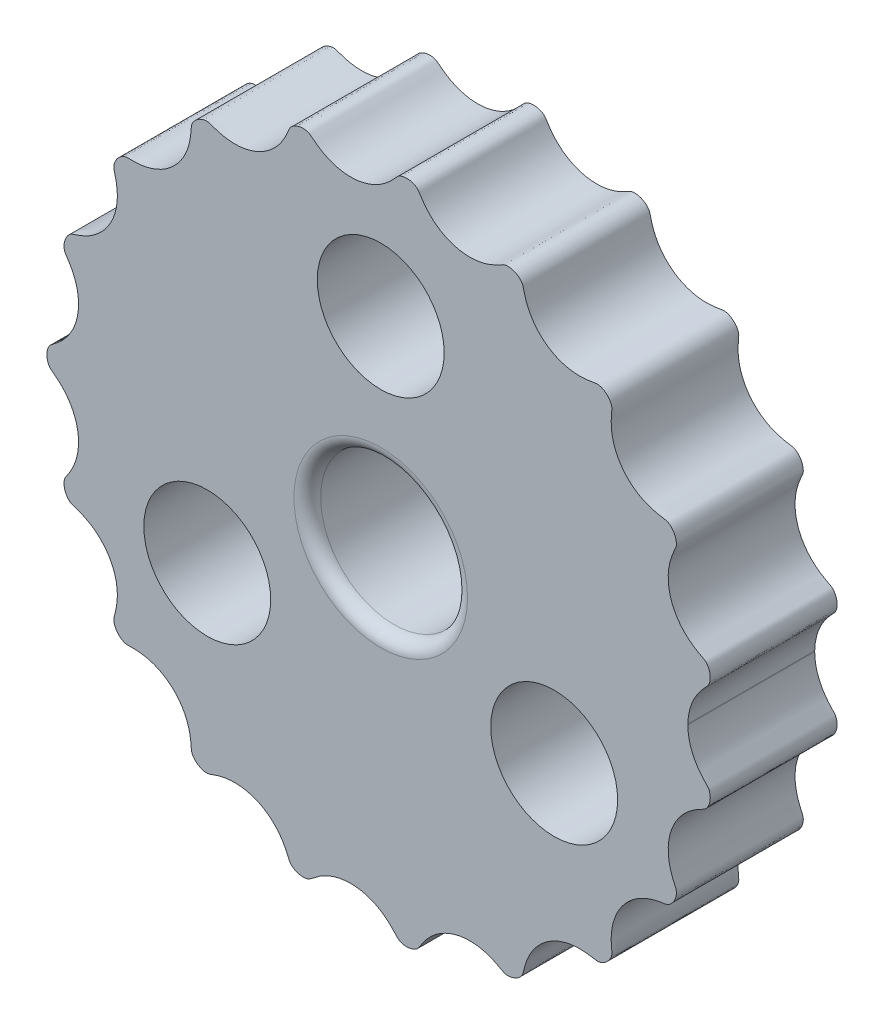
SolidWorks part; units mm, degrees
ref_plane "Ebene vorne" through (0, 0, 0) normal (0, 0, 1) x (1, 0, 0)
ref_plane "Ebene oben" through (0, 0, 0) normal (0, 1, 0) x (1, 0, 0)
ref_plane "Ebene rechts" through (0, 0, 0) normal (1, 0, 0) x (0, 0, -1)
sketch "Skizze1" plane through (0, 0, 0) normal (0, 0, 1) x (1, 0, 0)
  circle A0 centre (0, 0) radius 25
  dimension "D1" = 50
extrude "Aufsatz-Linear austragen1" add sketch "Skizze1" along normal blind 9.5 contours A0
sketch "Skizze3" plane through (0, 0, 9.5) normal (0, 0, 1) x (1, 0, 0)
  circle A0 centre (0, 25) radius 0.5
  circle A1 centre (0, 0) radius 25 construction
extrude "Schnitt-Linear austragen1" cut sketch "Skizze3" against normal up to next contours A0
pattern_circular "Kreismuster3" [suppressed] count 30 over 360 of bodies 102
sketch "Skizze9" plane through (0, 0, 9.5) normal (0, 0, 1) x (1, 0, 0)
  line L0 (23.0004, 0.0609) -> (23, 0)
  spline S0 degree 4 poles (21.8349, 10.4363) (21.7595, 10.2402) (21.6296, 9.8393) (21.51, 9.2154) (21.5169, 8.368) (21.6949, 7.529) (21.9996, 6.8362) (22.3616, 6.2918) (22.7278, 5.8789) (23.0126, 5.6175) (23.2743, 5.4145) (23.4929, 5.2661) (23.6607, 5.1622) (23.8217, 5.0701) (23.9556, 4.9977) (24.0711, 4.9376) (24.1728, 4.8842) (24.259, 4.8347) (24.3648, 4.7517) (24.4596, 4.6337) (24.5411, 4.4963) (24.6203, 4.3033) (24.6742, 4.0826) (24.6893, 3.8352) (24.654, 3.6047) (24.5939, 3.4337) (24.5231, 3.3149) (24.4482, 3.2274) (24.3391, 3.1139) (24.2149, 2.9815) (24.0838, 2.8346) (23.9185, 2.6346) (23.746, 2.4006) (23.5642, 2.1174) (23.3859, 1.7712) (23.2392, 1.419) (23.1381, 1.082) (23.0724, 0.8012) (23.0325, 0.5259) (23.0102, 0.3454) (22.9992, 0.0775) (22.999, -0.0665) (23.009, -0.3222) (23.0286, -0.4951) (23.0652, -0.7605) (23.1283, -1.0483) (23.2566, -1.484) (23.4559, -1.9318) (23.6809, -2.3132) (23.9099, -2.6224) (24.0743, -2.8241) (24.2067, -2.9723) (24.3336, -3.1084) (24.4467, -3.2256) (24.524, -3.3159) (24.583, -3.4156) (24.6246, -3.5208) (24.6638, -3.6686) (24.6852, -3.8609) (24.6735, -4.0869) (24.6205, -4.3068) (24.5464, -4.4848) (24.4695, -4.6144) (24.4037, -4.7024) (24.3311, -4.7784) (24.2516, -4.8395) (24.1377, -4.9039) (24.0001, -4.974) (23.846, -5.0565) (23.6352, -5.1762) (23.3933, -5.3292) (23.1212, -5.5276) (22.8316, -5.7799) (22.5655, -6.0569) (22.2617, -6.4361) (21.9548, -6.9332) (21.7249, -7.4811) (21.5829, -8.0653) (21.5273, -8.5636) (21.5216, -8.9708) (21.5541, -9.3694) (21.6218, -9.7561) (21.7087, -10.0818) (21.7995, -10.3483) (21.8842, -10.5632) (21.9558, -10.729) (22.0248, -10.8829) (22.0924, -11.0248) (22.1404, -11.1746) (22.1504, -11.3468) (22.1274, -11.5442) (22.061, -11.7619) (21.9505, -11.9788) (21.8083, -12.1674) (21.6614, -12.3022) (21.5247, -12.3914) (21.414, -12.4372) (21.3301, -12.4586) (21.2321, -12.4761) (21.1212, -12.4922) (20.9921, -12.5121) (20.8374, -12.539) (20.6763, -12.5709) (20.4655, -12.6198) (20.1205, -12.7175) (19.6539, -12.8972) (19.0899, -13.2109) (18.4957, -13.6939) (17.9798, -14.3033) (17.5818, -15.0184) (17.3599, -15.7125) (17.2758, -16.2728) (17.2579, -16.6757) (17.2603, -16.9123) (17.2683, -17.0871) (17.2802, -17.2498) (17.2921, -17.3816) (17.3037, -17.4944) (17.3123, -17.5952) (17.3148, -17.684) (17.3037, -17.7848) (17.2728, -17.8946) (17.2143, -18.0352) (17.1157, -18.1992) (16.9706, -18.3697) (16.7741, -18.5306) (16.5633, -18.6445) (16.3771, -18.7041) (16.228, -18.7183) (16.1024, -18.7064) (15.9827, -18.6847) (15.837, -18.6581) (15.664, -18.6292) (15.4825, -18.6042) (15.2505, -18.5802) (14.9676, -18.5655) (14.5429, -18.5729) (14.0693, -18.6361) (13.6043, -18.7559) (13.0666, -18.9667) (12.6278, -19.2052) (12.2149, -19.5036) (11.8389, -19.8586) (11.5583, -20.1838) (11.3157, -20.5303) (11.1115, -20.893) (10.9662, -21.2192) (10.865, -21.4994) (10.7941, -21.7329) (10.7511, -21.8937) (10.717, -22.0322) (10.6867, -22.159) (10.6596, -22.2741) (10.6135, -22.4098) (10.5273, -22.5357) (10.4274, -22.6442) (10.2911, -22.7583) (10.1265, -22.8625) (9.947, -22.94) (9.7581, -22.9885) (9.581, -23.009) (9.446, -23.0074) (9.3222, -22.9883) (9.215, -22.9494) (9.1367, -22.9105) (9.0374, -22.8556) (8.9163, -22.7867) (8.7704, -22.7082) (8.5994, -22.6214) (8.2969, -22.4821) (7.9364, -22.3488) (7.5146, -22.2402) (7.0313, -22.1759) (6.6328, -22.1607) (6.2298, -22.1836) (5.826, -22.2463) (5.4253, -22.3496) (5.032, -22.4941) (4.6565, -22.6767) (4.3023, -22.8948) (3.9755, -23.1429) (3.6777, -23.4168) (3.4441, -23.6748) (3.264, -23.904) (3.127, -24.0974) (3.026, -24.2496) (2.9434, -24.3794) (2.8771, -24.486) (2.8107, -24.5788) (2.7442, -24.6523) (2.6543, -24.7214) (2.5172, -24.8007) (2.3431, -24.8698) (2.129, -24.9172) (1.9104, -24.9257) (1.7254, -24.9049) (1.5597, -24.8634) (1.4272, -24.8123) (1.3018, -24.7374) (1.1919, -24.6254) (1.0929, -24.5126) (0.9862, -24.3949) (0.8714, -24.2728) (0.7167, -24.1173) (0.5166, -23.934) (0.1944, -23.6752) (-0.2816, -23.3734) (-0.8873, -23.1037) (-1.633, -22.9219) (-2.4119, -22.88) (-3.1838, -22.9833) (-3.829, -23.1953) (-4.2989, -23.431) (-4.6166, -23.6302) (-4.8236, -23.7746) (-4.9777, -23.8915) (-5.1193, -24.0037) (-5.2422, -24.1039) (-5.3368, -24.1704) (-5.4383, -24.2183) (-5.5428, -24.2496) (-5.6869, -24.2756) (-5.8715, -24.2822) (-6.0864, -24.2562) (-6.2931, -24.1927) (-6.4597, -24.1129) (-6.6006, -24.0204) (-6.7112, -23.9272) (-6.7966, -23.8241) (-6.8508, -23.7158) (-6.8984, -23.6058) (-6.9474, -23.4882) (-7.0086, -23.3469) (-7.0843, -23.183) (-7.1853, -22.982) (-7.3178, -22.7471) (-7.4915, -22.481) (-7.7159, -22.1922) (-7.9683, -21.919) (-8.2484, -21.6651) (-8.561, -21.4293) (-9, -21.1594) (-9.4852, -20.944) (-10.0058, -20.7949) (-10.5401, -20.7187) (-10.9664, -20.7017) (-11.386, -20.7263) (-11.7441, -20.7819) (-12.0407, -20.8508) (-12.2801, -20.9199) (-12.4645, -20.9804) (-12.619, -21.0347) (-12.7443, -21.0813) (-12.8432, -21.1127) (-12.9148, -21.1293) (-13.0155, -21.1409) (-13.1607, -21.1341) (-13.3458, -21.0947) (-13.5626, -21.0052) (-13.7727, -20.87) (-13.9463, -20.7079) (-14.067, -20.5439) (-14.1433, -20.3907) (-14.1772, -20.2506) (-14.1869, -20.1194) (-14.1984, -19.9464) (-14.2135, -19.7574) (-14.2357, -19.56) (-14.2744, -19.3096) (-14.3484, -18.9507) (-14.4988, -18.4602) (-14.7821, -17.8614) (-15.2347, -17.2299) (-15.8123, -16.6797) (-16.4915, -16.2457) (-17.1512, -15.9856) (-17.6884, -15.8653) (-18.0779, -15.8187) (-18.3444, -15.8008) (-18.5515, -15.7964) (-18.7472, -15.7971) (-18.9192, -15.8013) (-19.043, -15.798) (-19.1585, -15.7742) (-19.2639, -15.7342) (-19.3981, -15.6643) (-19.5524, -15.5524) (-19.7098, -15.3942) (-19.8355, -15.2104) (-19.9175, -15.0392) (-19.9694, -14.8748) (-19.9942, -14.7409) (-19.9941, -14.6091) (-19.9622, -14.4594) (-19.9209, -14.3132) (-19.8775, -14.147) (-19.8227, -13.9154) (-19.7703, -13.6388) (-19.7298, -13.3095) (-19.7155, -12.9316) (-19.7343, -12.5536) (-19.7865, -12.1771) (-19.8725, -11.8051) (-20.0235, -11.3478) (-20.2355, -10.9007) (-20.5061, -10.4779) (-20.8313, -10.0898) (-21.1296, -9.7984) (-21.4493, -9.5419) (-21.7859, -9.3207) (-22.0908, -9.1576) (-22.3541, -9.0395) (-22.5745, -8.9534) (-22.7489, -8.8919) (-22.9125, -8.8369) (-23.0664, -8.7897) (-23.2127, -8.7239) (-23.3488, -8.6133) (-23.48, -8.461) (-23.5959, -8.2631) (-23.6806, -8.0335) (-23.7223, -7.802) (-23.7216, -7.6015) (-23.6936, -7.4372) (-23.6459, -7.3113) (-23.587, -7.2131) (-23.5046, -7.0919) (-23.4135, -6.9559) (-23.317, -6.8055) (-23.1954, -6.601) (-23.0687, -6.3633) (-22.9383, -6.0757) (-22.7839, -5.6451) (-22.656, -5.1008) (-22.5992, -4.4221) (-22.6826, -3.6209) (-22.9272, -2.8308) (-23.2818, -2.1836) (-23.6363, -1.7308) (-23.9221, -1.4366) (-24.1011, -1.2722) (-24.239, -1.1546) (-24.372, -1.0482) (-24.4823, -0.963) (-24.578, -0.8915) (-24.662, -0.827) (-24.7323, -0.7672) (-24.8009, -0.6902) (-24.8613, -0.5932) (-24.925, -0.4573) (-24.9789, -0.2784) (-25.008, -0.0615) (-24.998, 0.1569) (-24.9616, 0.3399) (-24.9066, 0.5001) (-24.8504, 0.6156) (-24.7832, 0.7138) (-24.7061, 0.7903) (-24.6412, 0.8433) (-24.5549, 0.909) (-24.4487, 0.9887) (-24.3242, 1.0855) (-24.1833, 1.2011) (-24.0105, 1.3531) (-23.8111, 1.5469) (-23.5946, 1.788) (-23.3715, 2.0829) (-23.1734, 2.3976) (-23.0026, 2.7303) (-22.8251, 3.1685) (-22.6969, 3.6432) (-22.6277, 4.1442) (-22.6242, 4.6617) (-22.6664, 5.0951) (-22.7519, 5.5174) (-22.8777, 5.9244) (-23.0193, 6.2625) (-23.1587, 6.5356) (-23.2844, 6.7524) (-23.3883, 6.9169) (-23.4888, 7.0702) (-23.5875, 7.2108) (-23.6712, 7.3568) (-23.7142, 7.5309) (-23.7261, 7.7309) (-23.6995, 7.9535) (-23.6303, 8.1831) (-23.5263, 8.3908) (-23.4082, 8.549) (-23.2912, 8.6625) (-23.187, 8.7339) (-23.0968, 8.7758) (-22.9816, 8.8159) (-22.8484, 8.8583) (-22.6971, 8.9097) (-22.4871, 8.9859) (-22.2435, 9.0865) (-21.9662, 9.221) (-21.6596, 9.4005) (-21.366, 9.6063) (-21.0151, 9.8992) (-20.6164, 10.3191) (-20.2771, 10.8105) (-20.0144, 11.3636) (-19.8542, 11.8663) (-19.7673, 12.2789) (-19.7222, 12.6923) (-19.7169, 13.1024) (-19.7451, 13.4552) (-19.7902, 13.7494) (-19.8394, 13.9878) (-19.8839, 14.1718) (-19.9244, 14.3263) (-19.9596, 14.452) (-19.9815, 14.5509) (-19.9911, 14.6219) (-19.9935, 14.7217) (-19.9742, 14.8643) (-19.9195, 15.0445) (-19.8125, 15.2522) (-19.6794, 15.4254) (-19.5437, 15.5557) (-19.4017, 15.6607) (-19.2787, 15.7293) (-19.1504, 15.7794) (-19.0246, 15.7985) (-18.927, 15.8005) (-18.8133, 15.7991) (-18.6836, 15.7969) (-18.532, 15.7969) (-18.3106, 15.8023) (-18.0413, 15.8209) (-17.7248, 15.8628) (-17.3647, 15.941) (-16.9178, 16.0786) (-16.3974, 16.3085) (-15.8239, 16.6734) (-15.2485, 17.213) (-14.783, 17.8542) (-14.4878, 18.4827) (-14.3351, 18.9986) (-14.2627, 19.3751) (-14.2269, 19.6306) (-14.2075, 19.8274) (-14.1936, 20.0116) (-14.184, 20.1733) (-14.1697, 20.2905) (-14.1362, 20.4005) (-14.0873, 20.5015) (-14.0059, 20.6294) (-13.8804, 20.7742) (-13.7077, 20.9182) (-13.5127, 21.0276) (-13.335, 21.0939) (-13.1647, 21.1311) (-13.0232, 21.1444) (-12.8817, 21.1276) (-12.7469, 21.0817) (-12.6315, 21.0398) (-12.5001, 20.993) (-12.3519, 20.9431) (-12.1413, 20.8781) (-11.8655, 20.8075) (-11.5389, 20.7468) (-11.1616, 20.7097) (-10.7833, 20.7056) (-10.3038, 20.7432) (-9.7354, 20.8584) (-9.1818, 21.0633) (-8.6608, 21.3563) (-8.2599, 21.6542) (-7.9581, 21.9276) (-7.6875, 22.2243) (-7.4782, 22.5013) (-7.318, 22.7492) (-7.2006, 22.9556) (-7.1162, 23.1178) (-7.0401, 23.2775) (-6.9792, 23.4143) (-6.929, 23.5322) (-6.8829, 23.6417) (-6.8396, 23.7425) (-6.7732, 23.8583) (-6.6528, 23.9827) (-6.4911, 24.0996) (-6.2848, 24.1982) (-6.0489, 24.2635) (-5.8125, 24.2858) (-5.6133, 24.2679) (-5.4554, 24.2266) (-5.3475, 24.1752) (-5.2756, 24.1275) (-5.1963, 24.0667) (-5.1084, 23.9955) (-5.0052, 23.9133) (-4.8796, 23.817) (-4.7458, 23.7196) (-4.5657, 23.5973) (-4.2579, 23.4095) (-3.8065, 23.1883) (-3.1897, 22.9875) (-2.4297, 22.8812) (-1.6328, 22.9188) (-0.8411, 23.1135) (-0.1854, 23.421) (0.2799, 23.7378) (0.5861, 23.9964) (0.7572, 24.1576) (0.8795, 24.2813) (0.9904, 24.3996) (1.0788, 24.4971) (1.1534, 24.5815) (1.2215, 24.6556) (1.2849, 24.7171) (1.366, 24.7765) (1.4665, 24.8274) (1.6073, 24.879) (1.7912, 24.9173) (2.0109, 24.9275) (2.2284, 24.8982) (2.4076, 24.8457) (2.5635, 24.7759) (2.6787, 24.7064) (2.7776, 24.6216) (2.853, 24.522) (2.9089, 24.4353) (2.9741, 24.3312) (3.0513, 24.2111) (3.1673, 24.0378) (3.3314, 23.8136) (3.5412, 23.5623) (3.803, 23.2967) (4.0867, 23.0548) (4.3911, 22.8375) (4.7145, 22.6472) (5.1434, 22.4443) (5.6099, 22.2897) (6.1032, 22.1928) (6.6136, 22.1597) (7.04, 22.1755) (7.456, 22.233) (7.8578, 22.329) (8.1935, 22.443) (8.4659, 22.558) (8.6842, 22.6634) (8.8514, 22.7516) (9.0063, 22.8365) (9.1484, 22.9196) (9.3008, 22.9869) (9.4518, 23.0083) (9.5997, 23.0081) (9.7768, 22.9846) (9.9657, 22.9334) (10.1449, 22.8528) (10.3091, 22.7455) (10.4441, 22.6278) (10.5341, 22.5264) (10.6032, 22.4212) (10.6459, 22.3149) (10.6698, 22.2304) (10.6965, 22.1196) (10.7284, 21.9833) (10.7696, 21.8219) (10.8224, 21.6365) (10.926, 21.3181) (11.074, 20.9612) (11.2824, 20.576) (11.5658, 20.1761) (11.8273, 19.8724) (12.1194, 19.5924) (12.4404, 19.3397) (12.8767, 19.0608) (13.3474, 18.8414) (13.8414, 18.6865) (14.3466, 18.5977) (14.6978, 18.5693) (14.9983, 18.5678) (15.2424, 18.5806) (15.4319, 18.5983) (15.6163, 18.622) (15.7956, 18.651) (15.9629, 18.6804) (16.1188, 18.7114) (16.2634, 18.7186) (16.3919, 18.6957) (16.5434, 18.6484) (16.7128, 18.5663) (16.8932, 18.44) (17.0477, 18.2836) (17.1576, 18.1324) (17.2387, 17.9815) (17.2904, 17.8485) (17.3189, 17.7045) (17.3093, 17.5471) (17.2934, 17.3968) (17.2791, 17.2377) (17.2672, 17.07) (17.2581, 16.8499) (17.2594, 16.5774) (17.2886, 16.1632) (17.3914, 15.6061) (17.6071, 14.9758) (17.9828, 14.3047) (18.4824, 13.7066) (19.0811, 13.2137) (19.6713, 12.887) (20.16, 12.7034) (20.5195, 12.6059) (20.7644, 12.5521) (20.9536, 12.5182) (21.1309, 12.4903) (21.2868, 12.4679) (21.399, 12.4432) (21.5025, 12.4008) (21.5963, 12.345) (21.7134, 12.2561) (21.8437, 12.1238) (21.9702, 11.9469) (22.0634, 11.7504) (22.117, 11.5726) (22.1436, 11.4054) (22.149, 11.2598) (22.129, 11.1267) (22.0845, 11.0132) (22.035, 10.903) (21.9816, 10.7867) (21.919, 10.6454) (21.8499, 10.4782) (21.7706, 10.2666) (21.6878, 10.0086) (21.6103, 9.6986) (21.5509, 9.3355) (21.5224, 8.9626) (21.5272, 8.5827) (21.5787, 8.0866) (21.6972, 7.5846) (21.8865, 7.0905) (22.1457, 6.6199) (22.3909, 6.2662) (22.6666, 5.9438) (22.9679, 5.6541) (23.2503, 5.43) (23.5008, 5.2597) (23.7129, 5.1314) (23.8814, 5.0373) (24.0251, 4.9609) (24.1437, 4.9005) (24.2332, 4.8492) (24.2935, 4.8079) (24.37, 4.7415) (24.4633, 4.6297) (24.5599, 4.466) (24.6407, 4.2447) (24.683, 3.9972) (24.6804, 3.7586) (24.6403, 3.558) (24.5776, 3.3979) (24.4956, 3.2786) (24.4048, 3.1827) (24.2851, 3.0565) (24.1558, 2.9165) (24.0253, 2.7659) (23.8669, 2.5657) (23.6527, 2.2673) (23.442, 1.9019) (23.2546, 1.4742) (23.132, 1.0608) (23.0706, 0.7861) (23.0335, 0.5349) (23.0132, 0.3678) (23.0003, 0.1223) (22.9986, -0.0189) (23.0056, -0.2852) (23.0253, -0.4661) (23.0615, -0.7427) (23.1239, -1.029) (23.2494, -1.4644) (23.4447, -1.9094) (23.6681, -2.2941) (23.8991, -2.6086) (24.0657, -2.8141) (24.1984, -2.9632) (24.3246, -3.0987) (24.4356, -3.2143) (24.5132, -3.3018) (24.5877, -3.4196) (24.6374, -3.5547) (24.6701, -3.7073) (24.6838, -3.9154) (24.6644, -4.1417) (24.6, -4.381) (24.4916, -4.5912) (24.3759, -4.7394) (24.2736, -4.8247) (24.1898, -4.8749) (24.0901, -4.9279) (23.9765, -4.9865) (23.845, -5.0574) (23.6862, -5.1471) (23.5208, -5.2483) (23.3047, -5.3926) (23.0455, -5.59) (22.7627, -5.8442) (22.3976, -6.2458) (22.0314, -6.7792) (21.7172, -7.4627) (21.5252, -8.2962) (21.504, -9.1452) (21.6139, -9.7724) (21.7382, -10.176) (21.8113, -10.3736) knots 0 0 0 0 0 0.004237 0.008483 0.012729 0.016973 0.021413 0.023634 0.025855 0.02808 0.029193 0.030306 0.031182 0.032058 0.032934 0.033372 0.03381 0.034372 0.034934 0.036073 0.036831 0.037589 0.039124 0.04064 0.041779 0.042264 0.042749 0.043421 0.044093 0.045438 0.046411 0.047385 0.049332 0.051278 0.053223 0.055168 0.057112 0.0582 0.059287 0.060374 0.061462 0.062481 0.063501 0.064521 0.06554 0.067576 0.069612 0.073551 0.075471 0.07643 0.07739 0.078785 0.079482 0.08018 0.080676 0.081172 0.081811 0.082451 0.083753 0.085056 0.086348 0.086986 0.087623 0.08809 0.088558 0.089098 0.089639 0.090721 0.091672 0.092623 0.094526 0.09649 0.098454 0.100357 0.102259 0.106274 0.110193 0.112266 0.114339 0.116366 0.118392 0.120318 0.122244 0.123155 0.124065 0.124975 0.125886 0.126558 0.12723 0.128129 0.12933 0.130553 0.131784 0.13302 0.134061 0.134556 0.135052 0.135429 0.135805 0.136559 0.137312 0.138066 0.138968 0.13987 0.141675 0.145292 0.149024 0.152819 0.157032 0.161293 0.165414 0.167417 0.168419 0.16942 0.170182 0.170945 0.171707 0.172088 0.17247 0.172983 0.173496 0.174127 0.174758 0.176047 0.177335 0.178622 0.179842 0.180858 0.181239 0.181621 0.182383 0.183306 0.18423 0.185154 0.186077 0.188008 0.189939 0.193707 0.195683 0.19766 0.201566 0.203743 0.205919 0.208066 0.210213 0.212256 0.214298 0.215257 0.216216 0.217175 0.217654 0.218133 0.218845 0.219557 0.220527 0.221173 0.221818 0.22313 0.224442 0.22509 0.225738 0.226717 0.227156 0.227596 0.228035 0.228475 0.229441 0.230408 0.231375 0.232341 0.236155 0.238143 0.24013 0.242157 0.244184 0.24627 0.248355 0.250487 0.252618 0.254674 0.25673 0.258747 0.260763 0.261683 0.262604 0.263524 0.264444 0.264789 0.265133 0.265821 0.26644 0.267059 0.26832 0.269582 0.270836 0.271447 0.272058 0.273021 0.273691 0.274361 0.275205 0.27605 0.276894 0.277739 0.279628 0.281518 0.285219 0.28907 0.292926 0.296908 0.300855 0.304679 0.306545 0.307478 0.308411 0.309767 0.310445 0.311123 0.311607 0.31209 0.312702 0.313313 0.314555 0.3158 0.31704 0.317653 0.318265 0.319194 0.319946 0.320323 0.320699 0.321608 0.322518 0.323427 0.324337 0.326144 0.327952 0.329828 0.331704 0.333634 0.335564 0.337712 0.342077 0.344294 0.346435 0.348576 0.350665 0.352755 0.353733 0.35471 0.355688 0.356666 0.357036 0.357406 0.357777 0.358147 0.359078 0.360318 0.361577 0.362842 0.364095 0.365072 0.365667 0.366263 0.366989 0.367716 0.369169 0.370082 0.370996 0.372823 0.376553 0.380398 0.384283 0.388402 0.39254 0.396544 0.398494 0.399468 0.400443 0.401928 0.402671 0.403414 0.403914 0.404414 0.405044 0.405674 0.406958 0.408242 0.409517 0.410142 0.410767 0.411715 0.412247 0.41278 0.413844 0.414778 0.415711 0.417578 0.419518 0.421458 0.423328 0.425198 0.427172 0.429146 0.433023 0.435141 0.437259 0.439338 0.441417 0.443393 0.445369 0.446301 0.447232 0.448164 0.449096 0.449784 0.450473 0.451382 0.452594 0.453825 0.455064 0.456299 0.457303 0.457852 0.458401 0.459003 0.459604 0.460806 0.461705 0.462604 0.464401 0.466234 0.468066 0.471816 0.475642 0.479892 0.484207 0.488376 0.490424 0.491448 0.492472 0.493275 0.494078 0.494881 0.495283 0.495684 0.496212 0.496739 0.497357 0.497975 0.499232 0.500491 0.501743 0.502362 0.50298 0.503902 0.504323 0.504745 0.505167 0.505588 0.506507 0.507426 0.508345 0.509264 0.511146 0.513029 0.51487 0.51671 0.518635 0.520559 0.52439 0.526593 0.528795 0.530975 0.533155 0.535264 0.537372 0.538353 0.539334 0.540315 0.541296 0.542048 0.5428 0.543686 0.54487 0.546076 0.547289 0.548505 0.549524 0.55004 0.550557 0.551041 0.551525 0.552494 0.553378 0.554262 0.556029 0.557808 0.559586 0.561418 0.563249 0.567013 0.571226 0.573386 0.575547 0.57763 0.579713 0.581758 0.583803 0.584757 0.585711 0.586665 0.587619 0.587981 0.588342 0.588703 0.589064 0.589991 0.591226 0.592482 0.593745 0.594375 0.595005 0.596035 0.596581 0.597126 0.597563 0.597999 0.598872 0.599744 0.600617 0.602465 0.604312 0.606175 0.608037 0.611883 0.615748 0.619804 0.623847 0.62776 0.629667 0.63062 0.631574 0.63296 0.633653 0.634347 0.63484 0.635333 0.635965 0.636598 0.63789 0.639181 0.640471 0.641084 0.641696 0.642695 0.643315 0.643934 0.644554 0.645174 0.64613 0.647085 0.648997 0.65091 0.652822 0.654719 0.656616 0.660595 0.664476 0.666551 0.668626 0.67065 0.672674 0.674636 0.675617 0.676598 0.67746 0.678322 0.679184 0.679615 0.680046 0.680718 0.68139 0.682294 0.683501 0.68473 0.685967 0.68721 0.688256 0.688745 0.689234 0.689614 0.689994 0.690755 0.691516 0.692276 0.693184 0.694091 0.695906 0.699541 0.703294 0.707104 0.711296 0.715529 0.719623 0.721614 0.722609 0.723605 0.724363 0.72512 0.725878 0.726257 0.726636 0.727147 0.727657 0.728278 0.728898 0.730163 0.731429 0.732687 0.7333 0.733914 0.734868 0.735387 0.735906 0.736425 0.736945 0.737866 0.738787 0.740628 0.742544 0.74446 0.746298 0.748136 0.750076 0.752015 0.75585 0.758014 0.760177 0.762308 0.764439 0.766466 0.768494 0.769446 0.770399 0.771352 0.772304 0.773011 0.773717 0.774692 0.775341 0.77599 0.777308 0.778627 0.779278 0.77993 0.780912 0.781353 0.781795 0.782237 0.782678 0.78365 0.784622 0.785593 0.786565 0.790399 0.792398 0.794396 0.796432 0.798468 0.800544 0.802619 0.806855 0.808898 0.810941 0.812947 0.81395 0.814953 0.815868 0.816783 0.817698 0.818613 0.819297 0.819981 0.820603 0.821225 0.822492 0.82376 0.825019 0.825633 0.826247 0.827208 0.827886 0.828563 0.829411 0.830258 0.831106 0.831953 0.833852 0.83575 0.83947 0.843342 0.847212 0.851172 0.85509 0.858888 0.860742 0.861669 0.862595 0.863943 0.864616 0.86529 0.86577 0.866251 0.866866 0.86748 0.868728 0.86998 0.871226 0.871843 0.872459 0.87339 0.87415 0.87453 0.874909 0.875821 0.876733 0.877645 0.878557 0.880376 0.882194 0.884081 0.885968 0.887906 0.889845 0.894123 0.896327 0.898531 0.900659 0.902786 0.904866 0.906945 0.907918 0.90889 0.909862 0.910835 0.911203 0.911571 0.911939 0.912307 0.913243 0.914489 0.915755 0.917025 0.918283 0.919266 0.919863 0.920461 0.92119 0.921919 0.923377 0.924296 0.925215 0.927054 0.930802 0.932735 0.934668 0.935643 0.936618 0.937593 0.938568 0.939657 0.940745 0.941834 0.942922 0.944896 0.946869 0.950817 0.952789 0.953776 0.954762 0.956135 0.956821 0.957507 0.957996 0.958485 0.959623 0.960381 0.961139 0.962673 0.964189 0.965328 0.965881 0.966433 0.966863 0.967294 0.968154 0.969015 0.969875 0.970969 0.972064 0.974253 0.976438 0.978623 0.98299 0.987244 0.991499 0.995751 1 1 1 1 1 construction
  spline S1 degree 4 poles (23, 0) (23, -0.0443) (23.0016, -0.1335) (23.009, -0.3222) (23.0286, -0.4951) (23.0652, -0.7605) (23.1283, -1.0483) (23.2566, -1.484) (23.4559, -1.9318) (23.6809, -2.3132) (23.9099, -2.6224) (24.0743, -2.8241) (24.2067, -2.9723) (24.3336, -3.1084) (24.4467, -3.2256) (24.524, -3.3159) (24.583, -3.4156) (24.6246, -3.5208) (24.6638, -3.6686) (24.6852, -3.8609) (24.6735, -4.0869) (24.6205, -4.3068) (24.5464, -4.4848) (24.4695, -4.6144) (24.4037, -4.7024) (24.3311, -4.7784) (24.2516, -4.8395) (24.1377, -4.9039) (24.0001, -4.974) (23.846, -5.0565) (23.6352, -5.1762) (23.3933, -5.3292) (23.1212, -5.5276) (22.8316, -5.7799) (22.5655, -6.0569) (22.2617, -6.4361) (21.9548, -6.9332) (21.7249, -7.4811) (21.5829, -8.0653) (21.5273, -8.5636) (21.5216, -8.9708) (21.5541, -9.3694) (21.6218, -9.7561) (21.7087, -10.0818) (21.7995, -10.3483) (21.8842, -10.5632) (21.9558, -10.729) (22.0248, -10.8829) (22.0924, -11.0248) (22.1404, -11.1746) (22.1504, -11.3468) (22.1274, -11.5442) (22.061, -11.7619) (21.9505, -11.9788) (21.8083, -12.1674) (21.6614, -12.3022) (21.5247, -12.3914) (21.414, -12.4372) (21.3301, -12.4586) (21.2321, -12.4761) (21.1212, -12.4922) (20.9921, -12.5121) (20.8374, -12.539) (20.6763, -12.5709) (20.4655, -12.6198) (20.1205, -12.7175) (19.6539, -12.8972) (19.0899, -13.2109) (18.4957, -13.6939) (17.9798, -14.3033) (17.5818, -15.0184) (17.3599, -15.7125) (17.2758, -16.2728) (17.2579, -16.6757) (17.2603, -16.9123) (17.2683, -17.0871) (17.2802, -17.2498) (17.2921, -17.3816) (17.3037, -17.4944) (17.3123, -17.5952) (17.3148, -17.684) (17.3037, -17.7848) (17.2728, -17.8946) (17.2143, -18.0352) (17.1157, -18.1992) (16.9706, -18.3697) (16.7741, -18.5306) (16.5633, -18.6445) (16.3771, -18.7041) (16.228, -18.7183) (16.1024, -18.7064) (15.9827, -18.6847) (15.837, -18.6581) (15.664, -18.6292) (15.4825, -18.6042) (15.2505, -18.5802) (14.9676, -18.5655) (14.5429, -18.5729) (14.0693, -18.6361) (13.6043, -18.7559) (13.0666, -18.9667) (12.6278, -19.2052) (12.2149, -19.5036) (11.8389, -19.8586) (11.5583, -20.1838) (11.3157, -20.5303) (11.1115, -20.893) (10.9662, -21.2192) (10.865, -21.4994) (10.7941, -21.7329) (10.7511, -21.8937) (10.717, -22.0322) (10.6867, -22.159) (10.6596, -22.2741) (10.6135, -22.4098) (10.5273, -22.5357) (10.4274, -22.6442) (10.2911, -22.7583) (10.1265, -22.8625) (9.947, -22.94) (9.7581, -22.9885) (9.581, -23.009) (9.446, -23.0074) (9.3222, -22.9883) (9.215, -22.9494) (9.1367, -22.9105) (9.0374, -22.8556) (8.9163, -22.7867) (8.7704, -22.7082) (8.5994, -22.6214) (8.2969, -22.4821) (7.9364, -22.3488) (7.5146, -22.2402) (7.0313, -22.1759) (6.6328, -22.1607) (6.2298, -22.1836) (5.826, -22.2463) (5.4253, -22.3496) (5.032, -22.4941) (4.6565, -22.6767) (4.3023, -22.8948) (3.9755, -23.1429) (3.6777, -23.4168) (3.4441, -23.6748) (3.264, -23.904) (3.127, -24.0974) (3.026, -24.2496) (2.9434, -24.3794) (2.8771, -24.486) (2.8107, -24.5788) (2.7442, -24.6523) (2.6543, -24.7214) (2.5172, -24.8007) (2.3431, -24.8698) (2.129, -24.9172) (1.9104, -24.9257) (1.7254, -24.9049) (1.5597, -24.8634) (1.4272, -24.8123) (1.3018, -24.7374) (1.1919, -24.6254) (1.0929, -24.5126) (0.9862, -24.3949) (0.8714, -24.2728) (0.7167, -24.1173) (0.5166, -23.934) (0.1944, -23.6752) (-0.2816, -23.3734) (-0.8873, -23.1037) (-1.633, -22.9219) (-2.4119, -22.88) (-3.1838, -22.9833) (-3.829, -23.1953) (-4.2989, -23.431) (-4.6166, -23.6302) (-4.8236, -23.7746) (-4.9777, -23.8915) (-5.1193, -24.0037) (-5.2422, -24.1039) (-5.3368, -24.1704) (-5.4383, -24.2183) (-5.5428, -24.2496) (-5.6869, -24.2756) (-5.8715, -24.2822) (-6.0864, -24.2562) (-6.2931, -24.1927) (-6.4597, -24.1129) (-6.6006, -24.0204) (-6.7112, -23.9272) (-6.7966, -23.8241) (-6.8508, -23.7158) (-6.8984, -23.6058) (-6.9474, -23.4882) (-7.0086, -23.3469) (-7.0843, -23.183) (-7.1853, -22.982) (-7.3178, -22.7471) (-7.4915, -22.481) (-7.7159, -22.1922) (-7.9683, -21.919) (-8.2484, -21.6651) (-8.561, -21.4293) (-9, -21.1594) (-9.4852, -20.944) (-10.0058, -20.7949) (-10.5401, -20.7187) (-10.9664, -20.7017) (-11.386, -20.7263) (-11.7441, -20.7819) (-12.0407, -20.8508) (-12.2801, -20.9199) (-12.4645, -20.9804) (-12.619, -21.0347) (-12.7443, -21.0813) (-12.8432, -21.1127) (-12.9148, -21.1293) (-13.0155, -21.1409) (-13.1607, -21.1341) (-13.3458, -21.0947) (-13.5626, -21.0052) (-13.7727, -20.87) (-13.9463, -20.7079) (-14.067, -20.5439) (-14.1433, -20.3907) (-14.1772, -20.2506) (-14.1869, -20.1194) (-14.1984, -19.9464) (-14.2135, -19.7574) (-14.2357, -19.56) (-14.2744, -19.3096) (-14.3484, -18.9507) (-14.4988, -18.4602) (-14.7821, -17.8614) (-15.2347, -17.2299) (-15.8123, -16.6797) (-16.4915, -16.2457) (-17.1512, -15.9856) (-17.6884, -15.8653) (-18.0779, -15.8187) (-18.3444, -15.8008) (-18.5515, -15.7964) (-18.7472, -15.7971) (-18.9192, -15.8013) (-19.043, -15.798) (-19.1585, -15.7742) (-19.2639, -15.7342) (-19.3981, -15.6643) (-19.5524, -15.5524) (-19.7098, -15.3942) (-19.8355, -15.2104) (-19.9175, -15.0392) (-19.9694, -14.8748) (-19.9942, -14.7409) (-19.9941, -14.6091) (-19.9622, -14.4594) (-19.9209, -14.3132) (-19.8775, -14.147) (-19.8227, -13.9154) (-19.7703, -13.6388) (-19.7298, -13.3095) (-19.7155, -12.9316) (-19.7343, -12.5536) (-19.7865, -12.1771) (-19.8725, -11.8051) (-20.0235, -11.3478) (-20.2355, -10.9007) (-20.5061, -10.4779) (-20.8313, -10.0898) (-21.1296, -9.7984) (-21.4493, -9.5419) (-21.7859, -9.3207) (-22.0908, -9.1576) (-22.3541, -9.0395) (-22.5745, -8.9534) (-22.7489, -8.8919) (-22.9125, -8.8369) (-23.0664, -8.7897) (-23.2127, -8.7239) (-23.3488, -8.6133) (-23.48, -8.461) (-23.5959, -8.2631) (-23.6806, -8.0335) (-23.7223, -7.802) (-23.7216, -7.6015) (-23.6936, -7.4372) (-23.6459, -7.3113) (-23.587, -7.2131) (-23.5046, -7.0919) (-23.4135, -6.9559) (-23.317, -6.8055) (-23.1954, -6.601) (-23.0687, -6.3633) (-22.9383, -6.0757) (-22.7839, -5.6451) (-22.656, -5.1008) (-22.5992, -4.4221) (-22.6826, -3.6209) (-22.9272, -2.8308) (-23.2818, -2.1836) (-23.6363, -1.7308) (-23.9221, -1.4366) (-24.1011, -1.2722) (-24.239, -1.1546) (-24.372, -1.0482) (-24.4823, -0.963) (-24.578, -0.8915) (-24.662, -0.827) (-24.7323, -0.7672) (-24.8009, -0.6902) (-24.8613, -0.5932) (-24.925, -0.4573) (-24.9789, -0.2784) (-25.008, -0.0615) (-24.998, 0.1569) (-24.9616, 0.3399) (-24.9066, 0.5001) (-24.8504, 0.6156) (-24.7832, 0.7138) (-24.7061, 0.7903) (-24.6412, 0.8433) (-24.5549, 0.909) (-24.4487, 0.9887) (-24.3242, 1.0855) (-24.1833, 1.2011) (-24.0105, 1.3531) (-23.8111, 1.5469) (-23.5946, 1.788) (-23.3715, 2.0829) (-23.1734, 2.3976) (-23.0026, 2.7303) (-22.8251, 3.1685) (-22.6969, 3.6432) (-22.6277, 4.1442) (-22.6242, 4.6617) (-22.6664, 5.0951) (-22.7519, 5.5174) (-22.8777, 5.9244) (-23.0193, 6.2625) (-23.1587, 6.5356) (-23.2844, 6.7524) (-23.3883, 6.9169) (-23.4888, 7.0702) (-23.5875, 7.2108) (-23.6712, 7.3568) (-23.7142, 7.5309) (-23.7261, 7.7309) (-23.6995, 7.9535) (-23.6303, 8.1831) (-23.5263, 8.3908) (-23.4082, 8.549) (-23.2912, 8.6625) (-23.187, 8.7339) (-23.0968, 8.7758) (-22.9816, 8.8159) (-22.8484, 8.8583) (-22.6971, 8.9097) (-22.4871, 8.9859) (-22.2435, 9.0865) (-21.9662, 9.221) (-21.6596, 9.4005) (-21.366, 9.6063) (-21.0151, 9.8992) (-20.6164, 10.3191) (-20.2771, 10.8105) (-20.0144, 11.3636) (-19.8542, 11.8663) (-19.7673, 12.2789) (-19.7222, 12.6923) (-19.7169, 13.1024) (-19.7451, 13.4552) (-19.7902, 13.7494) (-19.8394, 13.9878) (-19.8839, 14.1718) (-19.9244, 14.3263) (-19.9596, 14.452) (-19.9815, 14.5509) (-19.9911, 14.6219) (-19.9935, 14.7217) (-19.9742, 14.8643) (-19.9195, 15.0445) (-19.8125, 15.2522) (-19.6794, 15.4254) (-19.5437, 15.5557) (-19.4017, 15.6607) (-19.2787, 15.7293) (-19.1504, 15.7794) (-19.0246, 15.7985) (-18.927, 15.8005) (-18.8133, 15.7991) (-18.6836, 15.7969) (-18.532, 15.7969) (-18.3106, 15.8023) (-18.0413, 15.8209) (-17.7248, 15.8628) (-17.3647, 15.941) (-16.9178, 16.0786) (-16.3974, 16.3085) (-15.8239, 16.6734) (-15.2485, 17.213) (-14.783, 17.8542) (-14.4878, 18.4827) (-14.3351, 18.9986) (-14.2627, 19.3751) (-14.2269, 19.6306) (-14.2075, 19.8274) (-14.1936, 20.0116) (-14.184, 20.1733) (-14.1697, 20.2905) (-14.1362, 20.4005) (-14.0873, 20.5015) (-14.0059, 20.6294) (-13.8804, 20.7742) (-13.7077, 20.9182) (-13.5127, 21.0276) (-13.335, 21.0939) (-13.1647, 21.1311) (-13.0232, 21.1444) (-12.8817, 21.1276) (-12.7469, 21.0817) (-12.6315, 21.0398) (-12.5001, 20.993) (-12.3519, 20.9431) (-12.1413, 20.8781) (-11.8655, 20.8075) (-11.5389, 20.7468) (-11.1616, 20.7097) (-10.7833, 20.7056) (-10.3038, 20.7432) (-9.7354, 20.8584) (-9.1818, 21.0633) (-8.6608, 21.3563) (-8.2599, 21.6542) (-7.9581, 21.9276) (-7.6875, 22.2243) (-7.4782, 22.5013) (-7.318, 22.7492) (-7.2006, 22.9556) (-7.1162, 23.1178) (-7.0401, 23.2775) (-6.9792, 23.4143) (-6.929, 23.5322) (-6.8829, 23.6417) (-6.8396, 23.7425) (-6.7732, 23.8583) (-6.6528, 23.9827) (-6.4911, 24.0996) (-6.2848, 24.1982) (-6.0489, 24.2635) (-5.8125, 24.2858) (-5.6133, 24.2679) (-5.4554, 24.2266) (-5.3475, 24.1752) (-5.2756, 24.1275) (-5.1963, 24.0667) (-5.1084, 23.9955) (-5.0052, 23.9133) (-4.8796, 23.817) (-4.7458, 23.7196) (-4.5657, 23.5973) (-4.2579, 23.4095) (-3.8065, 23.1883) (-3.1897, 22.9875) (-2.4297, 22.8812) (-1.6328, 22.9188) (-0.8411, 23.1135) (-0.1854, 23.421) (0.2799, 23.7378) (0.5861, 23.9964) (0.7572, 24.1576) (0.8795, 24.2813) (0.9904, 24.3996) (1.0788, 24.4971) (1.1534, 24.5815) (1.2215, 24.6556) (1.2849, 24.7171) (1.366, 24.7765) (1.4665, 24.8274) (1.6073, 24.879) (1.7912, 24.9173) (2.0109, 24.9275) (2.2284, 24.8982) (2.4076, 24.8457) (2.5635, 24.7759) (2.6787, 24.7064) (2.7776, 24.6216) (2.853, 24.522) (2.9089, 24.4353) (2.9741, 24.3312) (3.0513, 24.2111) (3.1673, 24.0378) (3.3314, 23.8136) (3.5412, 23.5623) (3.803, 23.2967) (4.0867, 23.0548) (4.3911, 22.8375) (4.7145, 22.6472) (5.1434, 22.4443) (5.6099, 22.2897) (6.1032, 22.1928) (6.6136, 22.1597) (7.04, 22.1755) (7.456, 22.233) (7.8578, 22.329) (8.1935, 22.443) (8.4659, 22.558) (8.6842, 22.6634) (8.8514, 22.7516) (9.0063, 22.8365) (9.1484, 22.9196) (9.3008, 22.9869) (9.4518, 23.0083) (9.5997, 23.0081) (9.7768, 22.9846) (9.9657, 22.9334) (10.1449, 22.8528) (10.3091, 22.7455) (10.4441, 22.6278) (10.5341, 22.5264) (10.6032, 22.4212) (10.6459, 22.3149) (10.6698, 22.2304) (10.6965, 22.1196) (10.7284, 21.9833) (10.7696, 21.8219) (10.8224, 21.6365) (10.926, 21.3181) (11.074, 20.9612) (11.2824, 20.576) (11.5658, 20.1761) (11.8273, 19.8724) (12.1194, 19.5924) (12.4404, 19.3397) (12.8767, 19.0608) (13.3474, 18.8414) (13.8414, 18.6865) (14.3466, 18.5977) (14.6978, 18.5693) (14.9983, 18.5678) (15.2424, 18.5806) (15.4319, 18.5983) (15.6163, 18.622) (15.7956, 18.651) (15.9629, 18.6804) (16.1188, 18.7114) (16.2634, 18.7186) (16.3919, 18.6957) (16.5434, 18.6484) (16.7128, 18.5663) (16.8932, 18.44) (17.0477, 18.2836) (17.1576, 18.1324) (17.2387, 17.9815) (17.2904, 17.8485) (17.3189, 17.7045) (17.3093, 17.5471) (17.2934, 17.3968) (17.2791, 17.2377) (17.2672, 17.07) (17.2581, 16.8499) (17.2594, 16.5774) (17.2886, 16.1632) (17.3914, 15.6061) (17.6071, 14.9758) (17.9828, 14.3047) (18.4824, 13.7066) (19.0811, 13.2137) (19.6713, 12.887) (20.16, 12.7034) (20.5195, 12.6059) (20.7644, 12.5521) (20.9536, 12.5182) (21.1309, 12.4903) (21.2868, 12.4679) (21.399, 12.4432) (21.5025, 12.4008) (21.5963, 12.345) (21.7134, 12.2561) (21.8437, 12.1238) (21.9702, 11.9469) (22.0634, 11.7504) (22.117, 11.5726) (22.1436, 11.4054) (22.149, 11.2598) (22.129, 11.1267) (22.0845, 11.0132) (22.035, 10.903) (21.9816, 10.7867) (21.919, 10.6454) (21.8499, 10.4782) (21.7706, 10.2666) (21.6878, 10.0086) (21.6103, 9.6986) (21.5509, 9.3355) (21.5224, 8.9626) (21.5272, 8.5827) (21.5787, 8.0866) (21.6972, 7.5846) (21.8865, 7.0905) (22.1457, 6.6199) (22.3909, 6.2662) (22.6666, 5.9438) (22.9679, 5.6541) (23.2503, 5.43) (23.5008, 5.2597) (23.7129, 5.1314) (23.8814, 5.0373) (24.0251, 4.9609) (24.1437, 4.9005) (24.2332, 4.8492) (24.2935, 4.8079) (24.37, 4.7415) (24.4633, 4.6297) (24.5599, 4.466) (24.6407, 4.2447) (24.683, 3.9972) (24.6804, 3.7586) (24.6403, 3.558) (24.5776, 3.3979) (24.4956, 3.2786) (24.4048, 3.1827) (24.2851, 3.0565) (24.1558, 2.9165) (24.0253, 2.7659) (23.8669, 2.5657) (23.6527, 2.2673) (23.442, 1.9019) (23.2546, 1.4742) (23.132, 1.0608) (23.0706, 0.7861) (23.0335, 0.5349) (23.0132, 0.3678) (23.0038, 0.1889) (23.0011, 0.1033) (23.0004, 0.0609) knots 0.061462 0.061462 0.061462 0.061462 0.061462 0.062481 0.063501 0.064521 0.06554 0.067576 0.069612 0.073551 0.075471 0.07643 0.07739 0.078785 0.079482 0.08018 0.080676 0.081172 0.081811 0.082451 0.083753 0.085056 0.086348 0.086986 0.087623 0.08809 0.088558 0.089098 0.089639 0.090721 0.091672 0.092623 0.094526 0.09649 0.098454 0.100357 0.102259 0.106274 0.110193 0.112266 0.114339 0.116366 0.118392 0.120318 0.122244 0.123155 0.124065 0.124975 0.125886 0.126558 0.12723 0.128129 0.12933 0.130553 0.131784 0.13302 0.134061 0.134556 0.135052 0.135429 0.135805 0.136559 0.137312 0.138066 0.138968 0.13987 0.141675 0.145292 0.149024 0.152819 0.157032 0.161293 0.165414 0.167417 0.168419 0.16942 0.170182 0.170945 0.171707 0.172088 0.17247 0.172983 0.173496 0.174127 0.174758 0.176047 0.177335 0.178622 0.179842 0.180858 0.181239 0.181621 0.182383 0.183306 0.18423 0.185154 0.186077 0.188008 0.189939 0.193707 0.195683 0.19766 0.201566 0.203743 0.205919 0.208066 0.210213 0.212256 0.214298 0.215257 0.216216 0.217175 0.217654 0.218133 0.218845 0.219557 0.220527 0.221173 0.221818 0.22313 0.224442 0.22509 0.225738 0.226717 0.227156 0.227596 0.228035 0.228475 0.229441 0.230408 0.231375 0.232341 0.236155 0.238143 0.24013 0.242157 0.244184 0.24627 0.248355 0.250487 0.252618 0.254674 0.25673 0.258747 0.260763 0.261683 0.262604 0.263524 0.264444 0.264789 0.265133 0.265821 0.26644 0.267059 0.26832 0.269582 0.270836 0.271447 0.272058 0.273021 0.273691 0.274361 0.275205 0.27605 0.276894 0.277739 0.279628 0.281518 0.285219 0.28907 0.292926 0.296908 0.300855 0.304679 0.306545 0.307478 0.308411 0.309767 0.310445 0.311123 0.311607 0.31209 0.312702 0.313313 0.314555 0.3158 0.31704 0.317653 0.318265 0.319194 0.319946 0.320323 0.320699 0.321608 0.322518 0.323427 0.324337 0.326144 0.327952 0.329828 0.331704 0.333634 0.335564 0.337712 0.342077 0.344294 0.346435 0.348576 0.350665 0.352755 0.353733 0.35471 0.355688 0.356666 0.357036 0.357406 0.357777 0.358147 0.359078 0.360318 0.361577 0.362842 0.364095 0.365072 0.365667 0.366263 0.366989 0.367716 0.369169 0.370082 0.370996 0.372823 0.376553 0.380398 0.384283 0.388402 0.39254 0.396544 0.398494 0.399468 0.400443 0.401928 0.402671 0.403414 0.403914 0.404414 0.405044 0.405674 0.406958 0.408242 0.409517 0.410142 0.410767 0.411715 0.412247 0.41278 0.413844 0.414778 0.415711 0.417578 0.419518 0.421458 0.423328 0.425198 0.427172 0.429146 0.433023 0.435141 0.437259 0.439338 0.441417 0.443393 0.445369 0.446301 0.447232 0.448164 0.449096 0.449784 0.450473 0.451382 0.452594 0.453825 0.455064 0.456299 0.457303 0.457852 0.458401 0.459003 0.459604 0.460806 0.461705 0.462604 0.464401 0.466234 0.468066 0.471816 0.475642 0.479892 0.484207 0.488376 0.490424 0.491448 0.492472 0.493275 0.494078 0.494881 0.495283 0.495684 0.496212 0.496739 0.497357 0.497975 0.499232 0.500491 0.501743 0.502362 0.50298 0.503902 0.504323 0.504745 0.505167 0.505588 0.506507 0.507426 0.508345 0.509264 0.511146 0.513029 0.51487 0.51671 0.518635 0.520559 0.52439 0.526593 0.528795 0.530975 0.533155 0.535264 0.537372 0.538353 0.539334 0.540315 0.541296 0.542048 0.5428 0.543686 0.54487 0.546076 0.547289 0.548505 0.549524 0.55004 0.550557 0.551041 0.551525 0.552494 0.553378 0.554262 0.556029 0.557808 0.559586 0.561418 0.563249 0.567013 0.571226 0.573386 0.575547 0.57763 0.579713 0.581758 0.583803 0.584757 0.585711 0.586665 0.587619 0.587981 0.588342 0.588703 0.589064 0.589991 0.591226 0.592482 0.593745 0.594375 0.595005 0.596035 0.596581 0.597126 0.597563 0.597999 0.598872 0.599744 0.600617 0.602465 0.604312 0.606175 0.608037 0.611883 0.615748 0.619804 0.623847 0.62776 0.629667 0.63062 0.631574 0.63296 0.633653 0.634347 0.63484 0.635333 0.635965 0.636598 0.63789 0.639181 0.640471 0.641084 0.641696 0.642695 0.643315 0.643934 0.644554 0.645174 0.64613 0.647085 0.648997 0.65091 0.652822 0.654719 0.656616 0.660595 0.664476 0.666551 0.668626 0.67065 0.672674 0.674636 0.675617 0.676598 0.67746 0.678322 0.679184 0.679615 0.680046 0.680718 0.68139 0.682294 0.683501 0.68473 0.685967 0.68721 0.688256 0.688745 0.689234 0.689614 0.689994 0.690755 0.691516 0.692276 0.693184 0.694091 0.695906 0.699541 0.703294 0.707104 0.711296 0.715529 0.719623 0.721614 0.722609 0.723605 0.724363 0.72512 0.725878 0.726257 0.726636 0.727147 0.727657 0.728278 0.728898 0.730163 0.731429 0.732687 0.7333 0.733914 0.734868 0.735387 0.735906 0.736425 0.736945 0.737866 0.738787 0.740628 0.742544 0.74446 0.746298 0.748136 0.750076 0.752015 0.75585 0.758014 0.760177 0.762308 0.764439 0.766466 0.768494 0.769446 0.770399 0.771352 0.772304 0.773011 0.773717 0.774692 0.775341 0.77599 0.777308 0.778627 0.779278 0.77993 0.780912 0.781353 0.781795 0.782237 0.782678 0.78365 0.784622 0.785593 0.786565 0.790399 0.792398 0.794396 0.796432 0.798468 0.800544 0.802619 0.806855 0.808898 0.810941 0.812947 0.81395 0.814953 0.815868 0.816783 0.817698 0.818613 0.819297 0.819981 0.820603 0.821225 0.822492 0.82376 0.825019 0.825633 0.826247 0.827208 0.827886 0.828563 0.829411 0.830258 0.831106 0.831953 0.833852 0.83575 0.83947 0.843342 0.847212 0.851172 0.85509 0.858888 0.860742 0.861669 0.862595 0.863943 0.864616 0.86529 0.86577 0.866251 0.866866 0.86748 0.868728 0.86998 0.871226 0.871843 0.872459 0.87339 0.87415 0.87453 0.874909 0.875821 0.876733 0.877645 0.878557 0.880376 0.882194 0.884081 0.885968 0.887906 0.889845 0.894123 0.896327 0.898531 0.900659 0.902786 0.904866 0.906945 0.907918 0.90889 0.909862 0.910835 0.911203 0.911571 0.911939 0.912307 0.913243 0.914489 0.915755 0.917025 0.918283 0.919266 0.919863 0.920461 0.92119 0.921919 0.923377 0.924296 0.925215 0.927054 0.930802 0.932735 0.934668 0.935643 0.936618 0.937593 0.938568 0.938568 0.938568 0.938568 0.938568
extrude "Schnitt-Linear austragen6" cut sketch "Skizze9" against normal blind 10 flip side to cut
sketch "Skizze23" plane through (0, 0, 0) normal (0, 0, -1) x (-1, 0, 0)
  circle A0 centre (0, 0) radius 9
extrude "Aufsatz-Linear austragen2" add sketch "Skizze23" along normal blind 0.5
sketch "Skizze21" plane through (0, 0, 0) normal (0, 0, -1) x (-1, 0, 0)
  circle A0 centre (0, 0) radius 5.5
  dimension "D1" = 11
extrude "Schnitt-Linear austragen11" cut sketch "Skizze21" against normal blind 9.5 and the other way blind 0.5
sketch "Skizze22" plane through (0, 0, 0) normal (0, 0, -1) x (-1, 0, 0)
  circle A0 centre (0, 0) radius 15
  circle A1 centre (0, 15) radius 4.75
  circle A2 centre (12.9904, -7.5) radius 4.75
  circle A3 centre (-12.9904, -7.5) radius 4.75
  point P12 (0, 0)
  dimension "D1" = 3
  dimension "D2" = 9.5
fillet "Verrundung1" radius 1 2 edges at (-5.5, 0, 9.5) (-5.5, 0, -0.5)
extrude "Schnitt-Linear austragen12" cut sketch "Skizze22" against normal blind 10 contours A1 | A2 | A3
